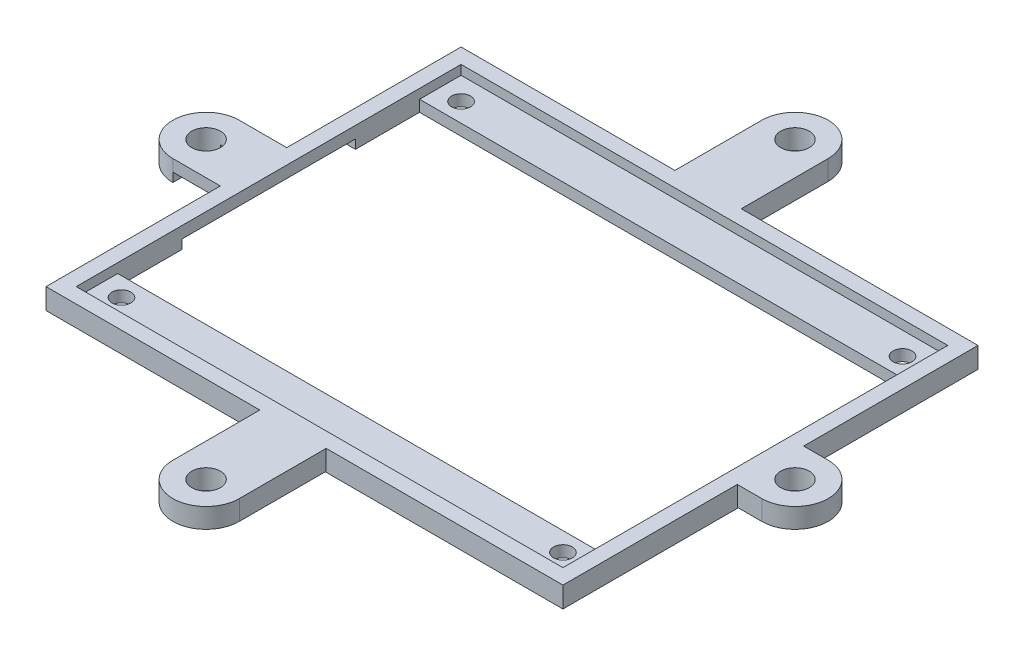
SolidWorks part; units mm, degrees
ref_plane "Front Plane" through (0, 0, 0) normal (0, 0, 1) x (1, 0, 0)
ref_plane "Top Plane" through (0, 0, 0) normal (0, 1, 0) x (1, 0, 0)
ref_plane "Right Plane" through (0, 0, 0) normal (1, 0, 0) x (0, 0, -1)
sketch "Sketch1" plane through (0, 0, 0) normal (0, 1, 0) x (1, 0, 0)
  line L1 (0, 0) -> (68.5, 0)
  line L2 (0, 0) -> (0, 55)
  line L3 (0, 55) -> (68.5, 55)
  line L4 (68.5, 0) -> (68.5, 55)
  dimension "D1" = 55
  dimension "D2" = 68.5
extrude "Boss-Extrude1" add sketch "Sketch1" along normal blind 1.5
sketch "Sketch2" plane through (0, 1.5, 0) normal (0, 1, 0) x (1, 0, 0)
  line L0 (2, 53) -> (2, 2)
  line L1 (2, 2) -> (66.5, 2)
  line L2 (66.5, 2) -> (66.5, 53)
  line L3 (66.5, 53) -> (2, 53)
  line L4 (0, 55) -> (0, 0)
  line L5 (0, 0) -> (68.5, 0)
  line L6 (68.5, 0) -> (68.5, 55)
  line L7 (68.5, 55) -> (0, 55)
  line L8 (0, 55) -> (0, 0)
  line L9 (0, 0) -> (68.5, 0)
  line L10 (68.5, 0) -> (68.5, 55)
  line L11 (68.5, 55) -> (0, 55)
  dimension "D1" = 0
  dimension "D2" = 2
extrude "Boss-Extrude2" add sketch "Sketch2" along normal blind 1.25
sketch "Sketch3" plane through (0, 1.5, 0) normal (0, 1, 0) x (1, 0, 0)
  line L0 (5, 53) -> (5, 50) construction
  line L1 (66.5, 53) -> (2, 53) construction
  line L2 (5, 50) -> (2, 50) construction
  line L3 (2, 53) -> (2, 2) construction
  line L4 (63.5, 5) -> (63.5, 2) construction
  line L5 (2, 2) -> (66.5, 2) construction
  line L6 (63.5, 5) -> (66.5, 5) construction
  line L7 (66.5, 2) -> (66.5, 53) construction
  line L8 (2, 53) -> (2, 2) construction
  line L10 (2, 7.5) -> (66.5, 7.5)
  line L11 (2, 7.5) -> (2, 47.5)
  line L12 (2, 47.5) -> (66.5, 47.5)
  line L13 (66.5, 7.5) -> (66.5, 47.5)
  circle A0 centre (5, 50) radius 1.25
  circle A1 centre (63.5, 50) radius 1.25
  circle A2 centre (63.5, 5) radius 1.25
  circle A3 centre (5, 5) radius 1.25
  dimension "D1" = 2.5
  dimension "D2" = 58.5
  dimension "D3" = 45
  dimension "D4" = 2.5
  dimension "D5" = 2.5
extrude "Cut-Extrude1" cut sketch "Sketch3" against normal blind 1.5
sketch "Sketch4" plane through (0, 0, 0) normal (-1, 0, 0) x (0, 0, 1)
  line L0 (-55, 0) -> (0, 0) construction
  line L1 (-39, 0) -> (-16, 0)
  line L2 (-39, 0) -> (-39, 1.2)
  line L3 (-39, 1.2) -> (-16, 1.2)
  line L4 (-16, 0) -> (-16, 1.2)
  point P6 (-27.5, 0)
  dimension "D1" = 23
  dimension "D2" = 1.2
extrude "Cut-Extrude2" cut sketch "Sketch4" against normal blind 3
sketch "Sketch5" plane through (0, 2.75, 0) normal (0, 1, 0) x (1, 0, 0)
  line L0 (0, 55) -> (0, 0) construction
  line L1 (68.5, 0) -> (68.5, 55) construction
  line L2 (-6.29, 27.5) -> (71.75, 27.5) construction
  line L3 (32.73, -11.52) -> (32.73, 66.52) construction
  line L4 (37.13, 55) -> (37.13, 66.52)
  line L5 (68.5, 55) -> (0, 55) construction
  line L6 (28.33, 66.52) -> (28.33, 55)
  line L7 (28.33, 55) -> (37.13, 55)
  line L8 (0, 31.9) -> (-6.29, 31.9)
  line L9 (-6.29, 23.1) -> (0, 23.1)
  line L10 (0, 31.9) -> (0, 23.1)
  line L11 (68.5, 31.9) -> (71.75, 31.9)
  line L12 (71.75, 23.1) -> (68.5, 23.1)
  line L13 (68.5, 31.9) -> (68.5, 23.1)
  line L14 (37.13, 0) -> (37.13, -11.52)
  line L15 (0, 0) -> (68.5, 0) construction
  line L16 (28.33, -11.52) -> (28.33, 0)
  line L17 (28.33, 0) -> (37.13, 0)
  circle A0 centre (-6.29, 27.5) radius 1.9
  circle A1 centre (71.75, 27.5) radius 1.9
  circle A2 centre (32.73, 66.52) radius 1.9
  circle A3 centre (32.73, -11.52) radius 1.9
  arc A4 (37.13, 66.52) -> (28.33, 66.52) centre (32.73, 66.52) ccw
  arc A5 (-6.29, 31.9) -> (-6.29, 23.1) centre (-6.29, 27.5) ccw
  arc A6 (71.75, 31.9) -> (71.75, 23.1) centre (71.75, 27.5) cw
  arc A7 (37.13, -11.52) -> (28.33, -11.52) centre (32.73, -11.52) cw
  point P7 (0, 27.5)
  point P12 (32.73, 27.5)
  line M11 (68.5, 55) -> (0, 55)
  line M12 (0, 55) -> (0, 0)
  line M13 (0, 0) -> (68.5, 0)
  line M14 (68.5, 0) -> (68.5, 55)
  dimension "D3" = 3.8
  dimension "D4" = 2.5
  dimension "D5" = 2.5
  dimension "D6" = 2.5
  dimension "D1" = 78.04
  dimension "D2" = 3.25
extrude "Boss-Extrude3" add sketch "Sketch5" against normal blind 2.625 contours A7 L14 L16 A3 M13 | A6 L11 L12 A1 M14 | L4 A4 L6 A2 M11 region at (32.73, 2.75, -62.1434) region at (32.73, 2.75, 7.1434) region at (70.125, 2.75, -31.7834)
extrude "Boss-Extrude4" add sketch "Sketch5<5>" against normal blind 1.55 contours L8 A5 L9 A0 M12 region at (-0.1385, 2.75, -27.5)
sketch "Sketch5<5>" plane through (0, 2.75, 0) normal (0, 1, 0) x (1, 0, 0) same geometry as "Sketch5"
sketch "Sketch6" plane through (0, 1.2, 0) normal (0, -1, 0) x (1, 0, 0)
  line L0 (-6.29, -25.6) -> (-6.29, -23.1)
  line L1 (-6.29, -31.9) -> (-6.29, -29.4)
  circle A0 centre (-6.29, -27.5) radius 1.9 construction
  arc A1 (-6.29, -23.1) -> (-6.29, -31.9) centre (-6.29, -27.5) ccw
  arc A2 (-6.29, -29.4) -> (-6.29, -25.6) centre (-6.29, -27.5) cw
extrude "Boss-Extrude5" add sketch "Sketch6" along normal blind 1.2
